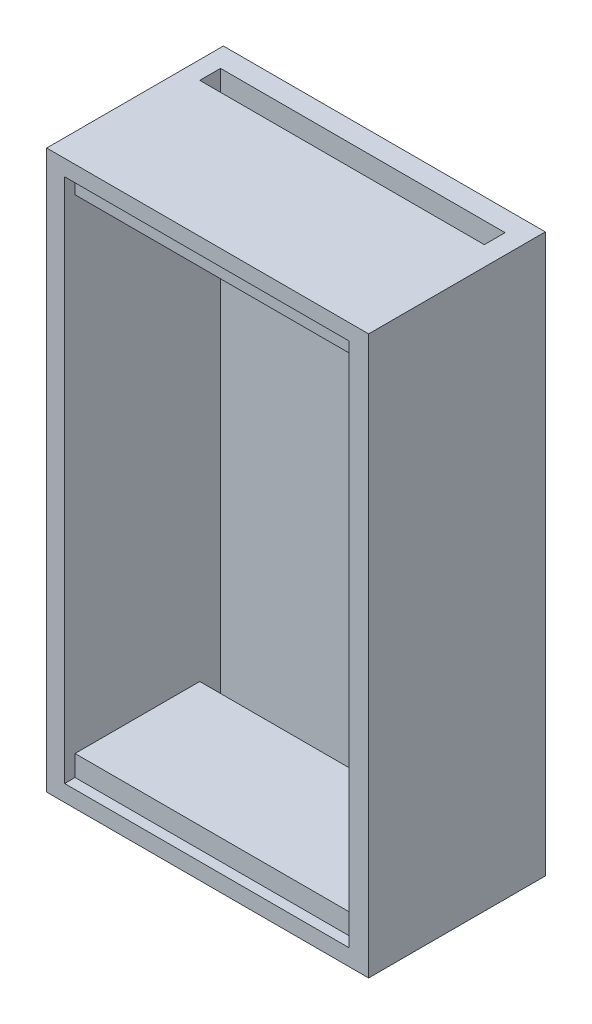
SolidWorks part; units mm, degrees
ref_plane "Front Plane" through (0, 0, 0) normal (0, 0, 1) x (1, 0, 0)
ref_plane "Top Plane" through (0, 0, 0) normal (0, 1, 0) x (1, 0, 0)
ref_plane "Right Plane" through (0, 0, 0) normal (1, 0, 0) x (0, 0, -1)
sketch "草图3" plane through (0, 0, 0) normal (0, 0, 1) x (1, 0, 0)
  line L6 (36.6895, -25.0841) -> (67.6642, -25.0841)
  line L7 (67.6642, -25.0841) -> (67.6642, -78.7564)
  line L10 (67.6642, -78.7564) -> (36.6895, -78.7564)
  line L11 (36.6895, -78.7564) -> (36.6895, -25.0841)
  line L12 (39.6768, -27.0841) -> (64.6769, -27.0841) construction
  line L13 (65.6642, -28.0714) -> (65.6642, -76.0715) construction
  line L14 (38.6895, -73.0389) -> (38.6895, -49.0971) construction
  line L16 (38.6895, -29.8002) -> (38.6895, -28.0714) construction
  line L17 (38.6895, -49.0971) -> (38.6895, -29.8461) construction
  line L18 (38.6895, -76.0715) -> (38.6895, -73.0389) construction
  line L19 (58.3492, -77.0595) -> (39.6768, -77.0588) construction
  line L20 (58.3492, -75.4585) -> (58.3492, -77.0595) construction
  line L21 (62.5529, -75.4458) -> (58.3619, -75.4458) construction
  line L22 (62.5656, -77.0715) -> (62.5656, -75.4585) construction
  line L23 (64.6769, -77.0588) -> (62.5656, -77.0966) construction
  line L24 (38.6895, -29.8002) -> (38.6895, -28.0714)
  line L25 (38.6895, -49.0971) -> (38.6895, -29.8461)
  line L26 (38.6895, -73.0389) -> (38.6895, -49.0971)
  line L27 (38.6895, -76.0715) -> (38.6895, -73.0389)
  line L28 (58.3492, -77.0595) -> (39.6768, -77.0588)
  line L29 (58.3492, -75.4585) -> (58.3492, -77.0595)
  line L30 (62.5529, -75.4458) -> (58.3619, -75.4458)
  line L31 (62.5656, -77.0715) -> (62.5656, -75.4585)
  line L32 (64.6769, -77.0588) -> (62.5656, -77.0966)
  line L33 (65.6642, -28.0714) -> (65.6642, -76.0715)
  line L34 (39.6768, -27.0841) -> (64.6769, -27.0841)
  arc A0 (38.6895, -76.0715) -> (39.6768, -77.0588) centre (39.6768, -76.0715) ccw construction
  arc A1 (64.6769, -77.0588) -> (65.6642, -76.0715) centre (64.6769, -76.0715) ccw construction
  arc A2 (65.6642, -28.0714) -> (64.6769, -27.0841) centre (64.6769, -28.0714) ccw construction
  arc A3 (39.6768, -27.0841) -> (38.6895, -28.0714) centre (39.6768, -28.0714) ccw construction
  arc A4 (38.6895, -76.0715) -> (39.6768, -77.0588) centre (39.6768, -76.0715) ccw
  arc A5 (64.6769, -77.0588) -> (65.6642, -76.0715) centre (64.6769, -76.0715) ccw
  arc A6 (65.6642, -28.0714) -> (64.6769, -27.0841) centre (64.6769, -28.0714) ccw
  arc A7 (39.6768, -27.0841) -> (38.6895, -28.0714) centre (39.6768, -28.0714) ccw
  dimension "D1" = 2
  dimension "D2" = 2
  dimension "D3" = 2
extrude "凸台-拉伸1" add sketch "草图3" along normal blind 17 contours L11 L10 L7 L6 region at (52.1769, -51.9203, 0)
sketch "草图5" plane through (0, 0, 17) normal (0, 0, 1) x (1, 0, 0)
  line L1 (38.4139, -26.6161) -> (65.7955, -26.6161)
  line L2 (65.7955, -26.6161) -> (65.7955, -77.1753)
  line L3 (65.7955, -77.1753) -> (38.4139, -77.1753)
  line L4 (38.4139, -77.1753) -> (38.4139, -26.6161)
extrude "切除-拉伸1" cut sketch "草图5" against normal blind 15
sketch "草图6" plane through (0, 0, 2) normal (0, 0, 1) x (1, 0, 0)
  line L0 (38.4139, -26.6161) -> (38.4139, -77.1753) construction
  line L1 (38.4139, -26.6161) -> (65.7955, -26.6161)
  line L2 (38.4139, -26.6161) -> (38.4139, -28.6161)
  line L3 (38.4139, -28.6161) -> (65.7955, -28.6161)
  line L4 (65.7955, -26.6161) -> (65.7955, -28.6161)
  line L5 (65.7955, -26.6161) -> (38.4139, -26.6161) construction
  line L6 (65.7955, -77.1753) -> (65.7955, -26.6161) construction
  line L7 (65.7955, -77.1753) -> (65.7955, -26.6161) construction
  line L8 (38.4139, -77.1753) -> (65.7955, -77.1753)
  line L9 (38.4139, -77.1753) -> (38.4139, -75.1753)
  line L10 (38.4139, -75.1753) -> (65.7955, -75.1753)
  line L11 (65.7955, -77.1753) -> (65.7955, -75.1753)
extrude "凸台-拉伸2" add sketch "草图6" along normal blind 14
sketch "草图8" plane through (0, -28.6161, 0) normal (0, -1, 0) x (1, 0, 0)
  line L0 (65.7955, 16) -> (65.7955, 2) construction
  line L1 (38.4139, 2) -> (65.7955, 2)
  line L2 (38.4139, 2) -> (38.4139, 4)
  line L3 (38.4139, 4) -> (65.7955, 4)
  line L4 (65.7955, 2) -> (65.7955, 4)
extrude "切除-拉伸2" cut sketch "草图8" against normal mid plane 106
